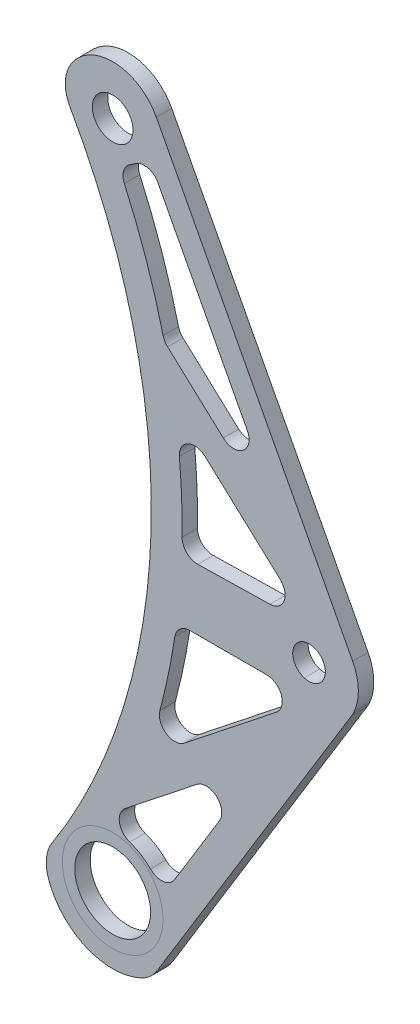
SolidWorks part; units mm, degrees
material "6061-T6 (SS)"
ref_plane "X-Y Datum" through (0, 0, 0) normal (0, 0, 1) x (1, 0, 0)
ref_plane "X-Z Datum" through (0, 0, 0) normal (0, 1, 0) x (1, 0, 0)
ref_plane "Y-Z Datum" through (0, 0, 0) normal (1, 0, 0) x (0, 0, -1)
sketch "Sketch1" plane through (0, 0, 0) normal (0, 0, 1) x (1, 0, 0)
  line L0 (0, 0) -> (0, 137.7747) construction
  line L1 (0, 137.7747) -> (40.4627, 60.9059) construction
  line L2 (40.4627, 60.9059) -> (0, 0) construction
  line L3 (-13.97, 0) -> (-10.16, 137.7747)
  line L4 (8.9905, 142.5072) -> (49.4532, 65.6383)
  line L5 (49.4532, 56.1734) -> (8.1778, -11.3263)
  circle A0 centre (0, 0) radius 7.8105
  circle A1 centre (40.4627, 60.9059) radius 3.3655
  circle A2 centre (0, 137.7747) radius 4.191
  arc A3 (-10.16, 137.7747) -> (8.9905, 142.5072) centre (0, 137.7747) cw
  arc A4 (49.4532, 65.6383) -> (49.4532, 56.1734) centre (40.4627, 60.9059) cw
  arc A5 (8.1778, -11.3263) -> (-13.97, 0) centre (0, 0) cw
  arc A6 (-10.16, 137.7747) -> (-13.97, 0) centre (-120.7988, 71.8942) cw
  circle A7 centre (0, 0) radius 11.5718
  point P16 (50.6227, 60.9059)
  dimension "D4" = 15.621
  dimension "D5" = 6.731
  dimension "D6" = 8.382
  dimension "D7" = 13.97
  dimension "D8" = 10.16
  dimension "D9" = 10.16
  dimension "D1" = 137.7747
  dimension "D2" = 86.868
  dimension "D3" = 73.1215
  dimension "D11" = 125.83
extrude "Boss-Extrude1" add sketch "Sketch1" along normal blind 3.175 contours A3 A6 A5 L5 A4 L4 A2 A1 A0 | A6 A7 A0 region at (18.3481, 68.0312, 0) region at (-11.2445, 0, 0)
sketch "Sketch2" plane through (0, 0, 3.175) normal (0, 0, 1) x (1, 0, 0)
  line L0 (10.1822, 4.1237) -> (40.9141, 54.3809)
  line L1 (49.4532, 56.1734) -> (8.1778, -11.3263) construction
  line L2 (43.0391, 66.9176) -> (6.9798, 135.4209)
  line L3 (8.9905, 142.5072) -> (49.4532, 65.6383) construction
  line L4 (40.3324, 67.4451) -> (14.2277, 66.9247)
  line L5 (40.4627, 54.3654) -> (13.1773, 54.3654)
  line L6 (40.3324, 67.4451) -> (12.6913, 92.8047)
  line L7 (36.2571, 79.8016) -> (10.6112, 103.3307)
  line L8 (40.9141, 54.3809) -> (6.7632, 27.3433)
  line L9 (31.3137, 38.6811) -> (1.9613, 15.4424)
  arc A4 (0.9614, 130.4717) -> (-0.1888, 10.9839) centre (-120.7988, 71.8942) cw
  arc A5 (-13.97, 0) -> (-10.16, 137.7747) centre (-120.7988, 71.8942) ccw construction
  circle A7 centre (0, 0) radius 10.9855
  circle A9 centre (40.4627, 60.9059) radius 6.5405
  circle A10 centre (0, 137.7747) radius 7.366
  circle A11 centre (0, 137.7747) radius 4.191 construction
  circle A12 centre (40.4627, 60.9059) radius 3.3655 construction
  circle A13 centre (0, 0) radius 7.8105 construction
  dimension "D3" = 3.175
  dimension "D1" = 3.175
  dimension "D2" = 3.175
  dimension "D6" = 6.35
  dimension "D4" = 5.08
  dimension "D5" = 6.35
  dimension "D7" = 6.35
  dimension "D8" = 6.35
extrude "Cut-Extrude1" cut sketch "Sketch2" against normal blind 6.35 contours A7 L0 L9 A4 | A9 L5 A4 L8 | L6 A4 L4 | A10 A4 L7 L2 region at (13.8635, 19.0589, 3.175) region at (20.6464, 45.5257, 3.175) region at (22.7038, 75.5881, 3.175) region at (15.7766, 109.4189, 3.175)
fillet "Fillet1" radius 3.175 14 edges at (1.9613, 15.4424, 1.5875) (-0.1888, 10.9839, 1.5875) (10.1822, 4.1237, 1.5875) (31.3137, 38.6811, 1.5875) (40.9141, 54.3809, 1.5875) (6.7632, 27.3433, 1.5875) (13.1773, 54.3654, 1.5875) (12.6913, 92.8047, 1.5875) (14.2277, 66.9247, 1.5875) (40.3324, 67.4451, 1.5875) (36.2571, 79.8016, 1.5875) (10.6112, 103.3307, 1.5875) (0.9614, 130.4717, 1.5875) (6.9798, 135.4209, 1.5875)
sketch "Sketch3" [suppressed] plane through (0, 0, 4.7625) normal (0, 0, 1) x (1, 0, 0)
  line L1 (13.9694, 0.1347) -> (39.7508, 21.6818)
  line L2 (9.979, 66.6708) -> (39.902, 40.8139)
  line L3 (55.423, 60.7241) -> (9.3949, 172.5239) construction
  line L6 (12.9992, 5.1168) -> (35.8725, 24.2335)
  line L8 (8.1778, -11.3263) -> (55.423, 52.9883) construction
  arc A0 (39.902, 40.8139) -> (35.8725, 24.2335) centre (43.2483, 31.2208) ccw
  arc A1 (-1.655, 13.8716) -> (12.9992, 5.1168) centre (0, 0) cw
  arc A3 (0.9228, 58.462) -> (-1.655, 13.8716) centre (-31.1833, 37.9483) cw
  circle A4 centre (43.2483, 31.2208) radius 10.16
  circle A5 centre (0, 0) radius 13.97
  arc A6 (0.9228, 58.462) -> (9.979, 66.6708) centre (0, 68.58) ccw
  circle A7 centre (0, 68.58) radius 10.16
  arc A8 (-5.9452, 60.3411) -> (-7.4548, 11.8147) centre (-23.0858, 36.5876) cw
  arc A9 (-13.4408, 9.525) -> (-10.5128, 62.23) centre (-35.7711, 37.1994) ccw construction
  dimension "D1" = 10.16
  dimension "D2" = 10.16
  dimension "D3" = 13.97
  dimension "D6" = 6.7275
  dimension "D9" = 12.7
  dimension "D7" = 38.1
  dimension "D4" = 29.81
  dimension "D5" = 5.08
  dimension "D8" = 5.08
  dimension "D11" = 75.318
extrude "Cut-Extrude2" [suppressed] cut sketch "Sketch3" against normal blind 6.35 contours A6 A3 A1 L6 A0 L2 | A5 L1 A4 L6 | L6 A0 L2 A6 A3 A1
sketch3d "3DSketch1" [suppressed]
  line L0 (0, 137.668, 3.175) -> (0, 137.668, 0) construction
  line L1 (40.5829, 60.8625, 3.175) -> (40.5829, 60.8625, 0) construction
  point P0 (0, 137.668, 3.175)
  point P1 (40.5829, 60.8625, 3.175)
fillet "Fillet2" [suppressed] radius 6.35
fillet "Fillet4" [suppressed] radius 6.35
ref_axis "Axis1" through (0, 137.7747, 3.175) along (0, 0, -1)
ref_axis "Axis2" through (40.4627, 60.9059, 3.175) along (0, 0, -1)
ref_plane "Plane1" through (23.5609, 4.1544, 0) normal (0.9848, 0.1736, 0) x (0, 0, -1)
ref_plane "Plane2" through (19.7196, -6.1043, 0) normal (0.9553, -0.2957, 0) x (0, 0, -1)
sketch "Sketch4" [suppressed] plane through (23.5426, 4.1512, 0) normal (0.9848, 0.1736, 0) x (0, 0, -1)
  line L0 (-3.175, 166.0937) -> (-3.175, 170.2847)
sketch "Sketch5" [suppressed] plane through (19.8415, -6.142, 0) normal (0.9553, -0.2957, 0) x (0, 0, -1)
  line L0 (-3.175, 70.1413) -> (-3.175, 11.4039)
  line L1 (-0.3461, 48.6622) -> (-0.3461, 36.6839)
split line "Split Line1"
split line "Split Line2" [suppressed]
ref_point "Point2"
ref_axis "Axis3" through (0, 0, 3.175) along (0, 0, -1)
sketch "Sketch6" plane through (0, 0, 3.175) normal (0, 0, -1) x (-1, 0, 0)
  circle A0 centre (0, 0) radius 10.3708
split line "Split Line3"
fillet "Fillet5" radius 7.62 4 edges at (-13.97, 0, 1.5875) (-10.16, 137.7747, 1.5875) (49.4532, 56.1734, 1.5875) (8.1778, -11.3263, 1.5875)
ref_point "Point4" [suppressed]
